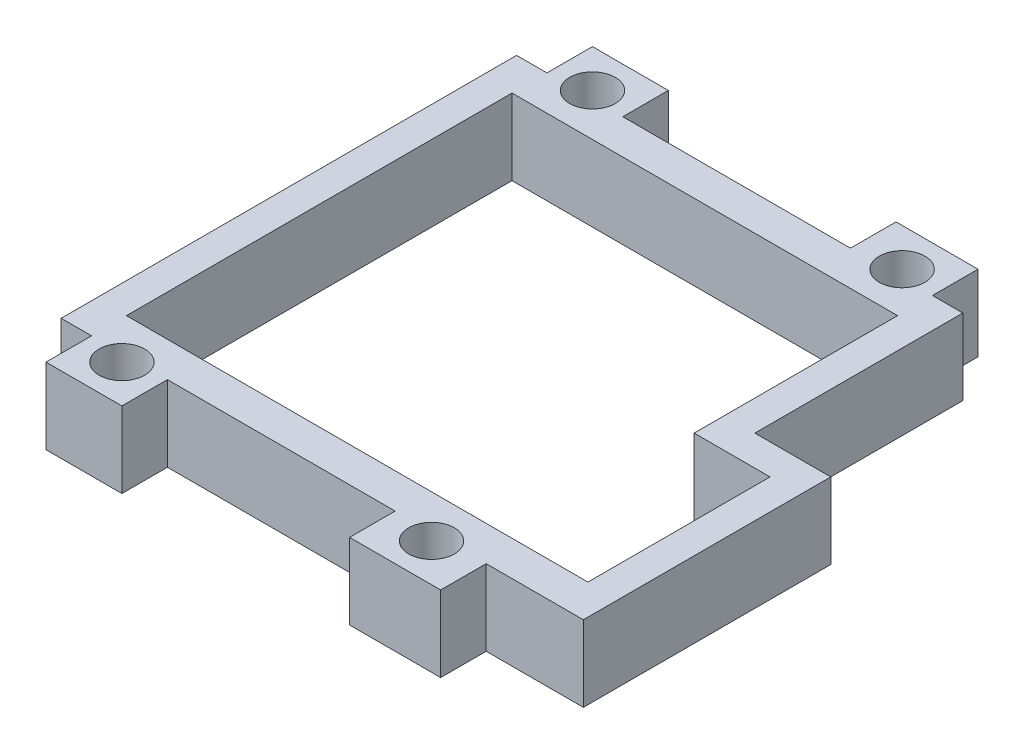
SolidWorks part; units mm, degrees
ref_plane "Front Plane" through (0, 0, 0) normal (0, 0, 1) x (1, 0, 0)
ref_plane "Top Plane" through (0, 0, 0) normal (0, 1, 0) x (1, 0, 0)
ref_plane "Right Plane" through (0, 0, 0) normal (1, 0, 0) x (0, 0, -1)
sketch "Sketch1" plane through (0, 0, 0) normal (0, 1, 0) x (1, 0, 0)
  line L1 (-17.2, -18) -> (17.2, -18)
  line L2 (-17.2, -18) -> (-17.2, 18)
  line L3 (-17.2, 18) -> (17.2, 18)
  line L4 (17.2, -18) -> (17.2, 18)
  line L5 (-17.2, -18) -> (17.2, 18) construction
  line L6 (-17.2, 18) -> (17.2, -18) construction
  point P0 (0, 0)
  dimension "D1" = 34.4
  dimension "D2" = 36
extrude "Boss-Extrude1" add sketch "Sketch1" along normal blind 5
sketch "Sketch4" plane through (0, 5, 0) normal (0, 1, 0) x (1, 0, 0)
  line L0 (17.2, 18) -> (-17.2, 18) construction
  line L1 (-15.2, 12.7) -> (10.2, 12.7)
  line L2 (-15.2, 12.7) -> (-15.2, -12.7)
  line L3 (-15.2, -12.7) -> (10.2, -12.7)
  line L4 (10.2, 12.7) -> (10.2, -12.7)
  line L5 (-17.2, -18) -> (17.2, -18) construction
  line L6 (-17.2, 18) -> (-17.2, -18) construction
  line L7 (17.2, -18) -> (17.2, 18) construction
  circle A0 centre (-12.7, 15.5) radius 1.5
  circle A1 centre (7.7, 15.5) radius 1.5
  circle A2 centre (7.7, -15.5) radius 1.5
  circle A3 centre (-12.7, -15.5) radius 1.5
  dimension "D5" = 3
  dimension "D6" = 3
  dimension "D7" = 3
  dimension "D8" = 3
  dimension "D1" = 25.4
  dimension "D2" = 25.4
  dimension "D3" = 5.3
  dimension "D4" = 5.3
  dimension "D9" = 2.8
  dimension "D10" = 2.8
  dimension "D11" = 2.8
  dimension "D12" = 2.8
  dimension "D13" = 2
  dimension "D14" = 4.5
  dimension "D15" = 4.5
  dimension "D16" = 9.5
  dimension "D17" = 9.5
extrude "Cut-Extrude2" cut sketch "Sketch4" against normal blind 5 contours A0
extrude "Cut-Extrude3" cut sketch "Sketch4<3>" against normal through all
sketch "Sketch4<3>" plane through (0, 5, 0) normal (0, 1, 0) x (1, 0, 0) same geometry as "Sketch4"
sketch "Sketch7" plane through (0, 5, 0) normal (0, 1, 0) x (1, 0, 0)
  line L1 (10.2, -12.7) -> (15.2, -12.7)
  line L2 (10.2, -12.7) -> (10.2, -0.7)
  line L3 (10.2, -0.7) -> (15.2, -0.7)
  line L4 (15.2, -12.7) -> (15.2, -0.7)
  dimension "D1" = 5
  dimension "D2" = 12
extrude "Cut-Extrude4" cut sketch "Sketch7" against normal blind 5
sketch "Sketch8" plane through (0, 5, 0) normal (0, 1, 0) x (1, 0, 0)
  line L0 (-17.2, -18) -> (17.2, -18) construction
  line L1 (-10.2, -18) -> (4.8, -18)
  line L2 (-10.2, -18) -> (-10.2, -15)
  line L3 (-10.2, -15) -> (4.8, -15)
  line L4 (4.8, -18) -> (4.8, -15)
  line L5 (-17.2, 18) -> (-17.2, -18) construction
  dimension "D1" = 15
  dimension "D2" = 7
  dimension "D3" = 3
extrude "Cut-Extrude5" cut sketch "Sketch8" against normal through all
sketch "Sketch9" plane through (0, 5, 0) normal (0, 1, 0) x (1, 0, 0)
  line L0 (4.8, -18) -> (4.8, -15) construction
  line L1 (17.2, -18) -> (10.8, -18)
  line L2 (17.2, -18) -> (17.2, -15)
  line L3 (17.2, -15) -> (10.8, -15)
  line L4 (10.8, -18) -> (10.8, -15)
  dimension "D1" = 6
  dimension "D2" = 3
extrude "Cut-Extrude6" cut sketch "Sketch9" against normal through all
sketch "Sketch10" plane through (0, 5, 0) normal (0, 1, 0) x (1, 0, 0)
  line L1 (-17.2, -18) -> (-15.2, -18)
  line L2 (-17.2, -18) -> (-17.2, -15)
  line L3 (-17.2, -15) -> (-15.2, -15)
  line L4 (-15.2, -18) -> (-15.2, -15)
  dimension "D1" = 2
  dimension "D2" = 3
extrude "Cut-Extrude7" cut sketch "Sketch10" against normal through all
sketch "Sketch11" plane through (0, 5, 0) normal (0, 1, 0) x (1, 0, 0)
  line L0 (17.2, 18) -> (-17.2, 18) construction
  line L1 (-17.2, 18) -> (-15.2, 18)
  line L2 (-17.2, 18) -> (-17.2, 15)
  line L3 (-17.2, 15) -> (-15.2, 15)
  line L4 (-15.2, 18) -> (-15.2, 15)
  line L5 (-10.2, 18) -> (4.8, 18)
  line L6 (-10.2, 18) -> (-10.2, 15)
  line L7 (-10.2, 15) -> (4.8, 15)
  line L8 (4.8, 18) -> (4.8, 15)
  line L9 (-17.2, 18) -> (-17.2, -15) construction
  dimension "D1" = 2
  dimension "D2" = 3
  dimension "D3" = 3
  dimension "D4" = 15
  dimension "D5" = 7
extrude "Cut-Extrude8" cut sketch "Sketch11" against normal through all
sketch "Sketch12" plane through (0, 5, 0) normal (0, 1, 0) x (1, 0, 0)
  line L0 (10.2, -0.7) -> (10.2, 12.7) construction
  line L1 (17.2, 18) -> (12.2, 18)
  line L2 (17.2, 18) -> (17.2, 1.3)
  line L3 (17.2, 1.3) -> (12.2, 1.3)
  line L4 (12.2, 18) -> (12.2, 1.3)
  line L5 (15.2, -0.7) -> (10.2, -0.7) construction
  dimension "D1" = 2
  dimension "D2" = 2
extrude "Cut-Extrude9" cut sketch "Sketch12" against normal through all
sketch "Sketch13" plane through (0, 5, 0) normal (0, 1, 0) x (1, 0, 0)
  line L1 (12.2, 18) -> (10.2, 18)
  line L2 (12.2, 18) -> (12.2, 15)
  line L3 (12.2, 15) -> (10.2, 15)
  line L4 (10.2, 18) -> (10.2, 15)
  dimension "D1" = 2
  dimension "D2" = 3
extrude "Cut-Extrude10" cut sketch "Sketch13" against normal through all
